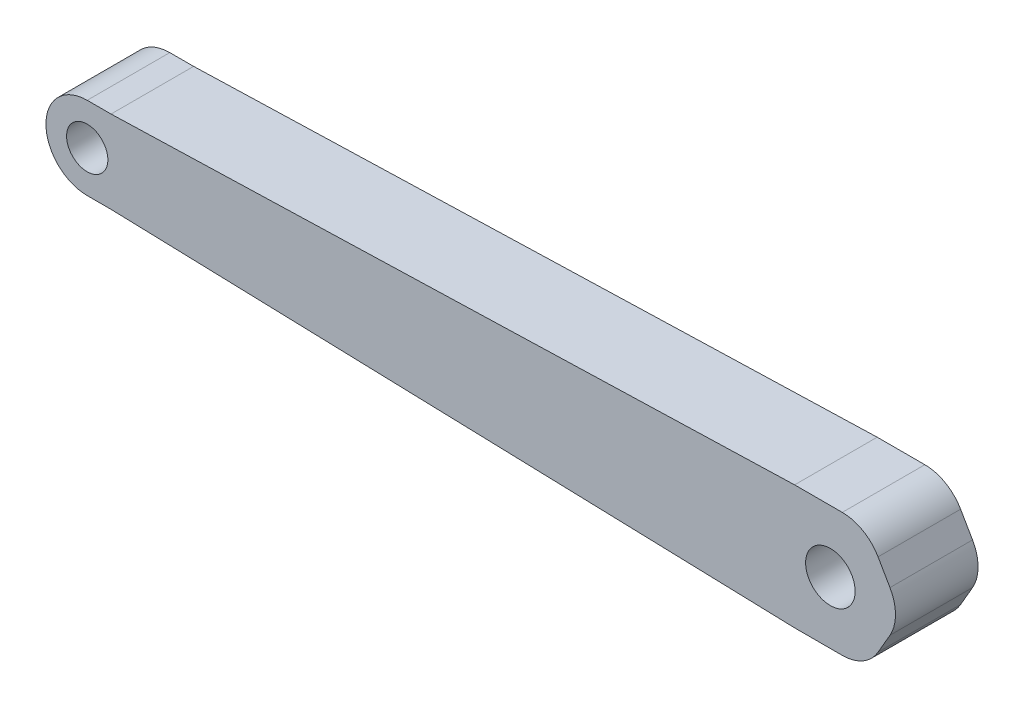
SolidWorks part; units mm, degrees
ref_plane "Front Plane" through (0, 0, 0) normal (0, 0, 1) x (1, 0, 0)
ref_plane "Top Plane" through (0, 0, 0) normal (0, 1, 0) x (1, 0, 0)
ref_plane "Right Plane" through (0, 0, 0) normal (1, 0, 0) x (0, 0, -1)
sketch "Sketch1" plane through (0, 0, 0) normal (0, 0, 1) x (1, 0, 0)
  line L0 (-114.3, 0) -> (114.3, 0) construction
  line L1 (-106.9677, 12.7) -> (103.3015, 19.05)
  line L2 (-99.6353, 0) -> (-106.9677, 12.7)
  line L3 (-106.9677, 12.7) -> (-121.6323, 12.7)
  line L4 (-121.6323, 12.7) -> (-128.9647, 0)
  line L5 (-128.9647, 0) -> (-121.6323, -12.7)
  line L6 (-121.6323, -12.7) -> (-106.9677, -12.7)
  line L7 (-106.9677, -12.7) -> (-99.6353, 0)
  line L8 (136.297, 0) -> (125.2985, 19.05)
  line L9 (125.2985, 19.05) -> (103.3015, 19.05)
  line L10 (103.3015, 19.05) -> (92.303, 0)
  line L11 (92.303, 0) -> (103.3015, -19.05)
  line L12 (103.3015, -19.05) -> (125.2985, -19.05)
  line L13 (125.2985, -19.05) -> (136.297, 0)
  line L14 (-106.9677, -12.7) -> (103.3015, -19.05)
  circle A0 centre (-114.3, 0) radius 6.35
  circle A1 centre (114.3, 0) radius 7.62
  circle A2 centre (-114.3, 0) radius 12.7 construction
  circle A3 centre (114.3, 0) radius 19.05 construction
  point P2 (0, 0)
  dimension "D1" = 228.6
  dimension "D2" = 15.24
  dimension "D5" = 38.1
  dimension "D6" = 265.2617
  dimension "D3" = 12.7
  dimension "D4" = 25.4
  dimension "D7" = 136.297
extrude "Boss-Extrude1" add sketch "Sketch1" along normal blind 25.4 contours L11 | L5 L2 L3 L4 A0 | L11 | L10 L11 L12 region at (3.6734, 0, 0) region at (-103.6375, 6.156, 0) region at (114.3, 18.468, 0)
fillet "Fillet3" radius 12.7 6 edges at (-128.9647, 0, 12.7) (-121.6323, 12.7, 12.7) (125.2985, -19.05, 12.7) (136.297, 0, 12.7) (125.2985, 19.05, 12.7) (-121.6323, -12.7, 12.7)
